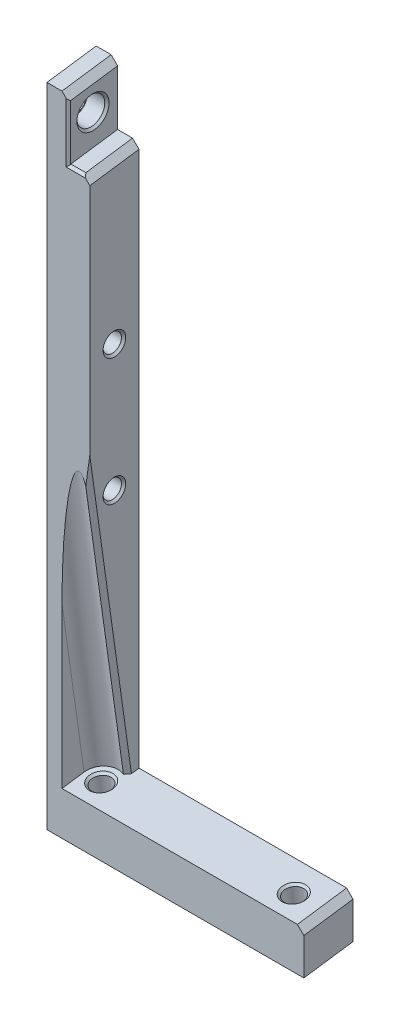
SolidWorks part; units mm, degrees
ref_plane "Top" through (0, 0, 0) normal (0, 0, 1) x (1, 0, 0)
ref_plane "Front" through (0, 0, 0) normal (0, 1, 0) x (1, 0, 0)
ref_plane "Right" through (0, 0, 0) normal (1, 0, 0) x (0, 0, -1)
sketch "Sketch4" plane through (0, 0, 0) normal (1, 0, 0) x (0, 0, -1)
  line L1 (0, 0) -> (11.5, 0)
  line L2 (0, 0) -> (0, 144)
  line L3 (0, 144) -> (11.5, 144)
  line L4 (11.5, 0) -> (11.5, 144)
  dimension "D1" = 11.5
  dimension "D2" = 144
extrude "Boss-Extrude2" add sketch "Sketch4" along normal blind 10
sketch "Sketch6" plane through (10, 0, 0) normal (1, 0, 0) x (0, 0, -1)
  line L0 (5.75, 0) -> (11.5, 0.8081)
  line L1 (0, 0) -> (11.5, 0) construction
  line L2 (11.5, 0) -> (11.5, 144) construction
  line L3 (11.5, 0.8081) -> (10.1083, 10.7108)
  line L4 (10.1083, 10.7108) -> (0.2056, 9.3191)
  line L5 (0.2056, 9.3191) -> (1.5973, -0.5836)
  line L6 (1.5973, -0.5836) -> (5.75, 0)
  line L7 (0, 144) -> (0, 0) construction
  dimension "D1" = 10
  dimension "D2" = 10
  dimension "D3" = 82
extrude "Boss-Extrude3" add sketch "Sketch6" along normal blind 50 and the other way blind 10
sketch "Sketch7" plane through (10, 0, 0) normal (1, 0, 0) x (0, 0, -1)
  line L0 (-3.1126, -1.2456) -> (11.8209, -3.029)
  line L2 (11.8209, -3.029) -> (11.8209, 0.8532)
  line L3 (11.8209, 0.8532) -> (-3.1126, -1.2456)
  line L4 (1.5973, -0.5836) -> (11.5, 0.8081) construction
extrude "Cut-Extrude2" cut sketch "Sketch7" against normal blind 10
sketch "Sketch8" plane through (0, 9.1102, 1.2804) normal (0, 0.9903, 0.1392) x (1, 0, 0)
  line L0 (10, 1.5005) -> (60, 1.5005) construction
  line L1 (60, 11.5005) -> (60, 1.5005) construction
  circle A0 centre (52.5, 6.5005) radius 2.25
  circle A1 centre (7.5, 6.5005) radius 2.25
  dimension "D2" = 4.5
  dimension "D3" = 4.5
  dimension "D1" = 45
  dimension "D4" = 5
  dimension "D5" = 7.5
extrude "Cut-Extrude3" cut sketch "Sketch8" against normal blind 10
sketch "Sketch11" plane through (0, 9.1102, 1.2804) normal (0, 0.9903, 0.1392) x (1, 0, 0)
  line L0 (3.5, 6.5005) -> (3.5, 0)
  line L1 (3.5, 0) -> (11.5, 0)
  line L3 (11.5, 0) -> (11.5, 6.5005)
  line L4 (10, 0) -> (0, 0) construction
  circle A0 centre (7.5, 6.5005) radius 4 construction
  arc A1 (11.5, 6.5005) -> (3.5, 6.5005) centre (7.5, 6.5005) ccw
  dimension "D1" = 8
extrude "Cut-Extrude4" cut sketch "Sketch11" along normal through all
sketch "Sketch12" plane through (60, 0, 0) normal (1, 0, 0) x (0, 0, -1)
  line L13 (1.5973, -0.5836) -> (0, -0.8081)
  line L14 (0, -0.8081) -> (0, 9.2902)
  line L16 (1.5973, -0.5836) -> (11.5, 0.8081) construction
  line L17 (0, 9.2902) -> (0, 0) construction
  line L18 (11.5, 0.8081) -> (11.5, 10.9064)
  line L20 (11.5, 10.9064) -> (10.1083, 10.7108)
  line L21 (10.1083, 10.7108) -> (11.5, 0.8081)
  line L22 (10.1083, 10.7108) -> (0.2056, 9.3191) construction
  line L23 (11.5, 0.8081) -> (11.5, 144) construction
  line L25 (11.5, 0.8081) -> (10.1083, 10.7108) construction
  line L26 (0, 9.2902) -> (0.2056, 9.3191)
  line L27 (0.2056, 9.3191) -> (1.5973, -0.5836)
  line L28 (0.2056, 9.3191) -> (1.5973, -0.5836) construction
  line L29 (5.1569, 10.0149) -> (0, 9.2902) construction
extrude "Boss-Extrude4" add sketch "Sketch12" against normal up to surface (60 mm away) up to face at (0, 48.0374, -4.3521)
sketch "Sketch13" plane through (10, 0, 0) normal (1, 0, 0) x (0, 0, -1)
  line L0 (11.5, 144) -> (11.5, 152)
  line L1 (11.5, 152) -> (0, 150.3838)
  line L2 (0, 150.3838) -> (0, 144)
  line L3 (0, 144) -> (11.5, 144)
  line L4 (11.5, 10.9064) -> (0, 9.2902) construction
  dimension "D1" = 8
extrude "Boss-Extrude5" add sketch "Sketch13" against normal blind 10
sketch "Sketch14" plane through (10, 0, 0) normal (1, 0, 0) x (0, 0, -1)
  line L0 (11.5, 10.9064) -> (11.5, 152) construction
  circle A0 centre (5.75, 144) radius 3.25
  dimension "D2" = 6.5
  dimension "D1" = 8
  dimension "D3" = 5.75
extrude "Cut-Extrude5" cut sketch "Sketch14" against normal blind 10
sketch "Sketch18" plane through (10, 0, 0) normal (1, 0, 0) x (0, 0, -1)
  line L0 (5.75, 99.6) -> (5.75, 70)
  line L1 (11.5, 10.9064) -> (11.5, 152) construction
  dimension "D1" = 5.75
  dimension "D2" = 29.6
  dimension "D3" = 70
hole_wizard "M4 Clearance Hole1" positions "Sketch19" profile "Sketch20" hole size "M4" standard "DIN" end condition through all
sketch "Sketch19" plane through (10, 0, 0) normal (1, 0, 0) x (0, 0, -1)
  point P0 (5.75, 70)
  point P3 (5.75, 99.6)
sketch "Sketch20" plane through (10, 70, -5.75) normal (0, 1, 0) x (0, 0, -1)
  line L0 (0, 0) -> (0, 10)
  line L1 (0, 10) -> (2.15, 10)
  line L2 (2.15, 10) -> (2.15, 0)
  line L5 (2.15, 0) -> (0, 0)
  line L11 (0, -6.35) -> (0, 107.95) construction
  dimension "Thru Hole Dia." = 4.3
  dimension "Thru Hole Depth" = 10
sketch "Sketch24" plane through (10, 0, 0) normal (1, 0, 0) x (0, 0, -1)
  line L0 (11.5, 152) -> (0, 150.3838)
  line L1 (0, 150.3838) -> (0, 136)
  line L2 (0, 150.3838) -> (0, 69.1445) construction
  line L3 (0, 136) -> (11.5, 137.6162)
  line L4 (11.5, 10.9064) -> (11.5, 152) construction
  line L5 (11.5, 137.6162) -> (11.5, 152)
  circle A0 centre (5.75, 144) radius 3.25 construction
  dimension "D1" = 8
extrude "Cut-Extrude7" cut sketch "Sketch24" against normal blind 5
chamfer "Chamfer2" distance 0.5 angle 45 10 edges at (10, 70, -7.9) (0, 70, -7.9) (10, 99.6, -7.9) (0, 99.6, -7.9) (0, 144, -9) (7.5, 9.7018, -2.9288) (7.5, -0.2009, -4.3206) (52.5, 9.7018, -2.9288) (52.5, -0.2009, -4.3206) (5, 144, -9)
chamfer "Chamfer4" distance 1.5 angle 45 1 edges at (10, 39.797, -4.1245) first distance on face at (10, 70, -3.1)
chamfer "Chamfer5" distance 0.5 angle 45 2 edges at (7.5, 136, 0) (5, 143.1919, 0) first distance on face at (15.0065, 72.7513, 0)
chamfer "Chamfer6" distance 1.5 angle 45 2 edges at (5, 151.227, -6) (10, 136.849, -6.0409)
chamfer "Chamfer7" distance 1.5 angle 45 1 edges at (60, 10.0983, -5.75)
